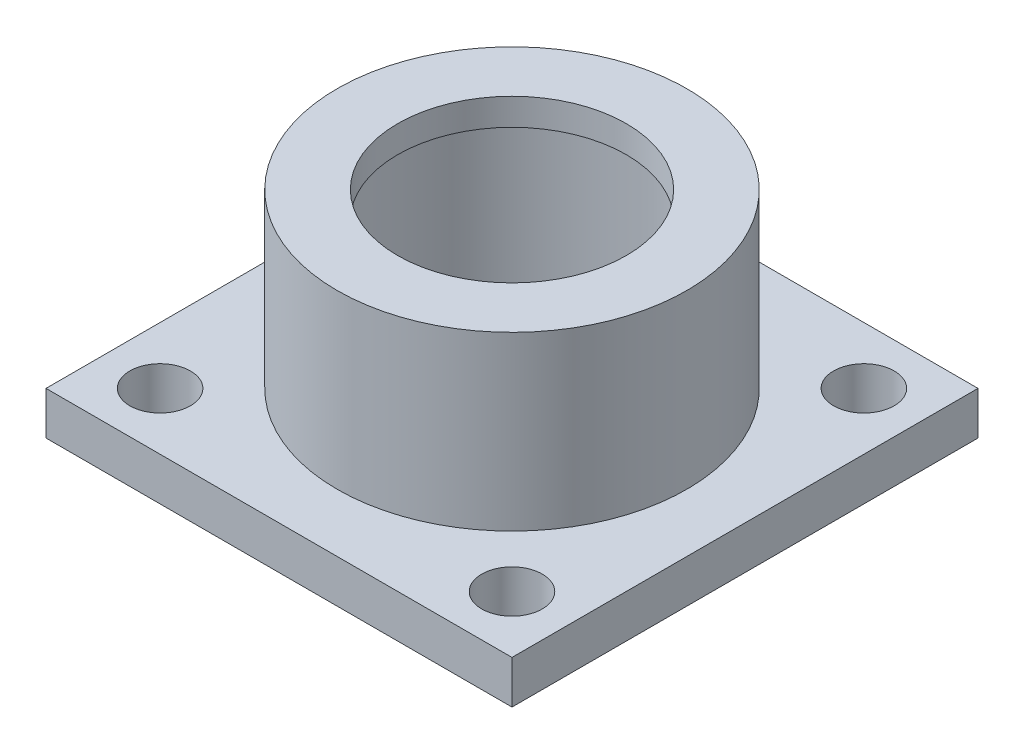
SolidWorks part; units mm, degrees
ref_plane "Front Plane" through (0, 0, 0) normal (0, 0, 1) x (1, 0, 0)
ref_plane "Top Plane" through (0, 0, 0) normal (0, 1, 0) x (1, 0, 0)
ref_plane "Right Plane" through (0, 0, 0) normal (1, 0, 0) x (0, 0, -1)
ref_axis "X" through (-88.99, 0, 0) along (1, 0, 0)
ref_axis "Y" through (0, 0, -88.99) along (0, 0, 1)
ref_axis "Z" through (0, 55, 0) along (0, -1, 0)
sketch "Sketch1" plane through (0, 0, 0) normal (0, 0, 1) x (1, 0, 0)
  line L0 (0, 31.4651) -> (0, -37.3488) construction
  line L1 (-24.5, 0) -> (-11, 0)
  line L2 (-13, 3.2) -> (-13, 16)
  line L3 (-13, 16) -> (-8.5, 16)
  line L5 (-8.5, 16) -> (-8.5, 14)
  line L6 (-8.5, 14) -> (-11, 14)
  line L7 (-11, 14) -> (-11, 0)
  line L8 (-13, 3.2) -> (-24.5, 3.2)
  line L9 (-24.5, 3.2) -> (-24.5, 0)
  dimension "D1" = 22
  dimension "D2" = 14
  dimension "D3" = 2
  dimension "D4" = 2
  dimension "D5" = 3.2
  dimension "D6" = 17
  dimension "D7" = 49
revolve "Revolve1" add sketch "Sketch1" angle 360 about L0
hole_wizard "M4 Clearance Hole1" positions "Sketch2" profile "Sketch3" hole size "M4" standard "DIN" end condition through all
sketch "Sketch2" plane through (0, 3.2, 0) normal (0, 1, 0) x (1, 0, 0)
  line L6 (13.0815, -13.0815) -> (-13.0815, -13.0815)
  line L7 (13.0815, -13.0815) -> (13.0815, 13.0815)
  line L8 (13.0815, 13.0815) -> (-13.0815, 13.0815)
  line L9 (-13.0815, -13.0815) -> (-13.0815, 13.0815)
  line L10 (13.0815, -13.0815) -> (-13.0815, 13.0815) construction
  line L11 (13.0815, 13.0815) -> (-13.0815, -13.0815) construction
  circle A1 centre (0, 0) radius 18.5
  point P63 (-13.0815, 13.0815)
  point P66 (13.0815, 13.0815)
  point P69 (13.0815, -13.0815)
  point P72 (-13.0815, -13.0815)
  dimension "D1" = 37
sketch "Sketch3" plane through (-13.0815, 3.2, 13.0815) normal (1, 0, 0) x (0, 0, 1)
  line L0 (0, 0) -> (0, 3.2)
  line L1 (0, 3.2) -> (2.25, 3.2)
  line L2 (2.25, 3.2) -> (2.25, 0)
  line L5 (2.25, 0) -> (0, 0)
  line L11 (0, -6.35) -> (0, 107.95) construction
  dimension "Thru Hole Dia." = 4.5
  dimension "Thru Hole Depth" = 3.2
sketch "Sketch5" plane through (0, 3.2, 0) normal (0, 1, 0) x (1, 0, 0)
  line L1 (17.3241, -17.3241) -> (-17.3241, -17.3241)
  line L2 (17.3241, -17.3241) -> (17.3241, 17.3241)
  line L3 (17.3241, 17.3241) -> (-17.3241, 17.3241)
  line L4 (-17.3241, -17.3241) -> (-17.3241, 17.3241)
  line L5 (17.3241, -17.3241) -> (-17.3241, 17.3241) construction
  line L6 (17.3241, 17.3241) -> (-17.3241, -17.3241) construction
  line L7 (42.9238, -32.5331) -> (-42.9238, -32.5331)
  line L8 (42.9238, -32.5331) -> (42.9238, 32.5331)
  line L9 (42.9238, 32.5331) -> (-42.9238, 32.5331)
  line L10 (-42.9238, -32.5331) -> (-42.9238, 32.5331)
  line L11 (42.9238, -32.5331) -> (-42.9238, 32.5331) construction
  line L12 (42.9238, 32.5331) -> (-42.9238, -32.5331) construction
  circle A0 centre (0, 0) radius 24.5 construction
  point P0 (0, 0)
  point P8 (0, 0)
extrude "Cut-Extrude2" cut sketch "Sketch5" against normal blind 10
